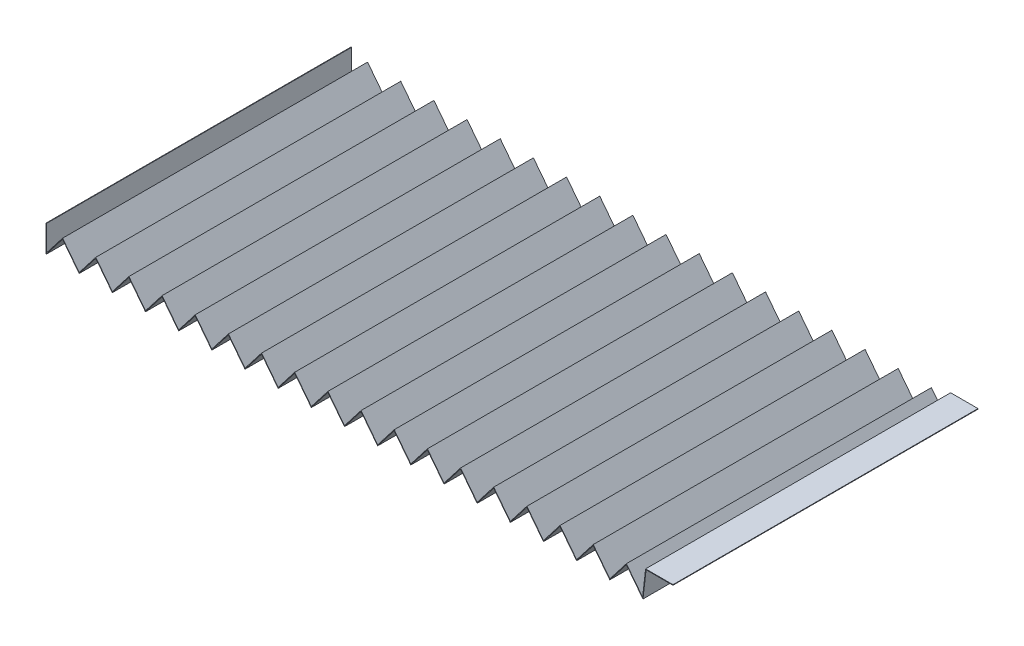
SolidWorks part; units mm, degrees
ref_plane "Front Plane" through (0, 0, 0) normal (0, 0, 1) x (1, 0, 0)
ref_plane "Top Plane" through (0, 0, 0) normal (0, 1, 0) x (1, 0, 0)
ref_plane "Right Plane" through (0, 0, 0) normal (1, 0, 0) x (0, 0, -1)
sketch "Sketch1" plane through (0, 0, 0) normal (0, 0, 1) x (1, 0, 0)
  line L0 (0, 0) -> (9.2424, 11.941)
  line L1 (9.2424, 11.941) -> (18.4849, 0)
  line L2 (0, 0) -> (511, 0) construction
  line L3 (18.4849, 0) -> (27.7273, 11.941)
  line L4 (27.7273, 11.941) -> (36.9698, 0)
  line L5 (36.9698, 0) -> (46.2122, 11.941)
  line L6 (46.2122, 11.941) -> (55.4547, 0)
  line L7 (55.4547, 0) -> (64.6971, 11.941)
  line L8 (64.6971, 11.941) -> (73.9396, 0)
  line L9 (73.9396, 0) -> (83.182, 11.941)
  line L10 (83.182, 11.941) -> (92.4245, 0)
  line L11 (92.4245, 0) -> (101.6669, 11.941)
  line L12 (101.6669, 11.941) -> (110.9094, 0)
  line L13 (110.9094, 0) -> (120.1518, 11.941)
  line L14 (120.1518, 11.941) -> (129.3943, 0)
  line L15 (129.3943, 0) -> (138.6367, 11.941)
  line L16 (138.6367, 11.941) -> (147.8792, 0)
  line L17 (147.8792, 0) -> (157.1216, 11.941)
  line L18 (157.1216, 11.941) -> (166.3641, 0)
  line L19 (0, 0) -> (0, 15.1)
  line L20 (166.3641, 0) -> (175.6065, 11.941)
  line L21 (175.6065, 11.941) -> (184.849, 0)
  line L22 (184.849, 0) -> (194.0914, 11.941)
  line L23 (194.0914, 11.941) -> (203.3339, 0)
  line L24 (203.3339, 0) -> (212.5763, 11.941)
  line L25 (212.5763, 11.941) -> (221.8188, 0)
  line L26 (221.8188, 0) -> (231.0612, 11.941)
  line L27 (231.0612, 11.941) -> (240.3037, 0)
  line L28 (240.3037, 0) -> (249.5461, 11.941)
  line L29 (249.5461, 11.941) -> (258.7886, 0)
  line L30 (258.7886, 0) -> (268.031, 11.941)
  line L31 (268.031, 11.941) -> (277.2735, 0)
  line L32 (277.2735, 0) -> (286.5159, 11.941)
  line L33 (286.5159, 11.941) -> (295.7584, 0)
  line L34 (295.7584, 0) -> (305.0008, 11.941)
  line L35 (305.0008, 11.941) -> (314.2433, 0)
  line L36 (314.2433, 0) -> (323.4857, 11.941)
  line L37 (323.4857, 11.941) -> (332.7282, 0)
  line L38 (332.7282, 0) -> (334.4631, 15)
  line L39 (334.4631, 15) -> (349.4631, 15)
  line L40 (347.4631, 13.6) -> (347.4631, 34.6) construction
  point P29 (347.4631, 24.1)
  dimension "D1" = 511
  dimension "D2" = 15.1
  dimension "D3" = 15
  dimension "D4" = 18.4849
  dimension "D6" = 15
  dimension "D7" = 2
  dimension "D5" = 18
extrude "Extrude-Thin1" add sketch "Sketch1" along normal mid plane 170 thin thin type one direction reverse wall 0.3
